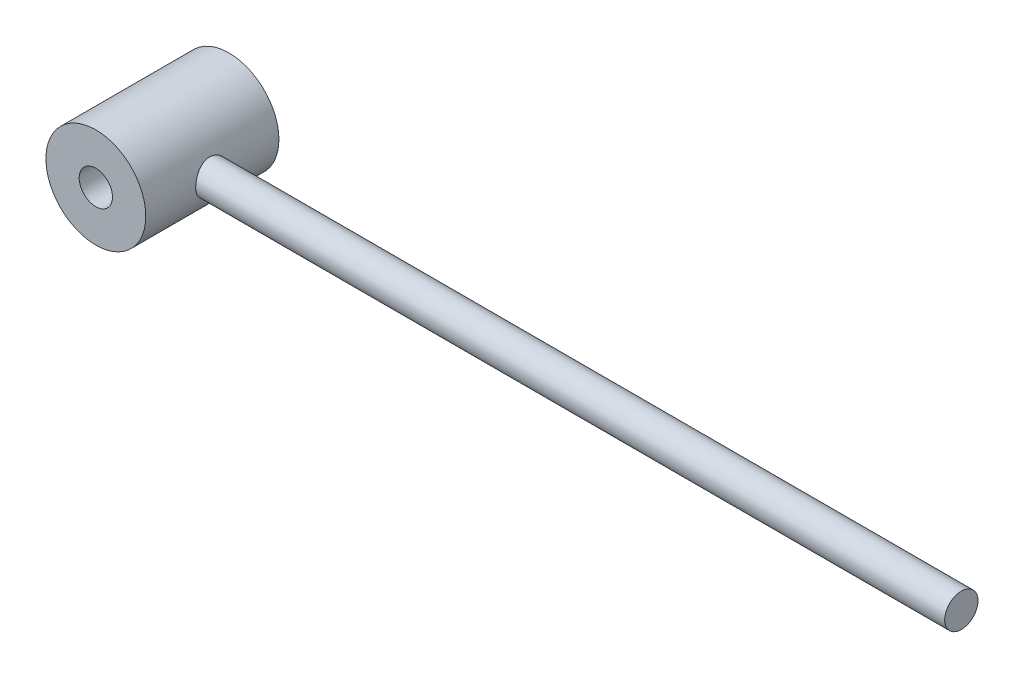
SolidWorks part; units mm, degrees
ref_plane "Front" through (0, 0, 0) normal (0, 0, 1) x (1, 0, 0)
ref_plane "Top" through (0, 0, 0) normal (0, 1, 0) x (1, 0, 0)
ref_plane "Right" through (0, 0, 0) normal (1, 0, 0) x (0, 0, -1)
sketch "Sketch1" plane through (0, 0, 0) normal (1, 0, 0) x (0, 0, -1)
  circle A0 centre (0, 0) radius 6.35
  dimension "D1" = 12.7
extrude "Boss-Extrude1" add sketch "Sketch1" along normal blind 304.8
sketch "Sketch2" plane through (0, 0, 0) normal (0, 0, 1) x (1, 0, 0)
  circle A0 centre (0, 0) radius 19.05
  dimension "D1" = 38.1
extrude "Boss-Extrude2" add sketch "Sketch2" along normal blind 25.4 and the other way blind 25.4
sketch "Sketch3" plane through (0, 0, 25.4) normal (0, 0, 1) x (1, 0, 0)
  circle A1 centre (0, 0) radius 6.35
  dimension "D1" = 12.7
extrude "Cut-Extrude1" cut sketch "Sketch3" against normal up to next
